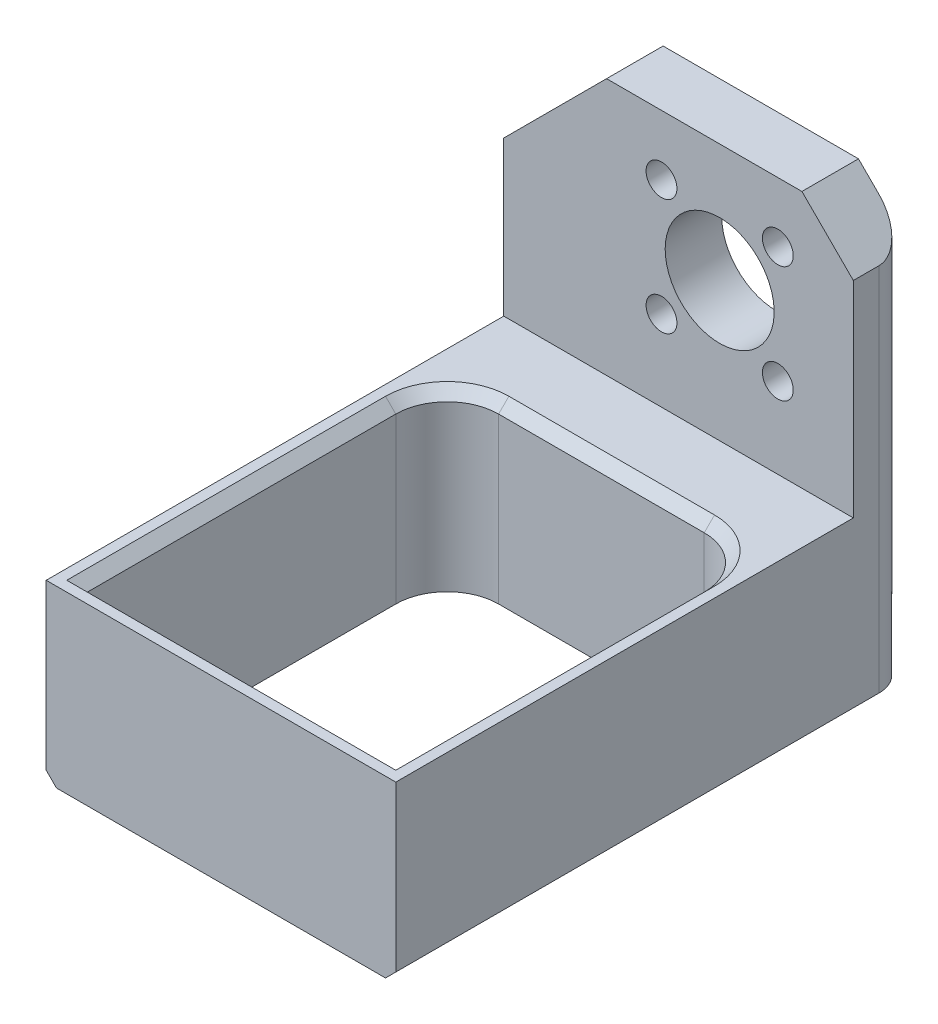
SolidWorks part; units mm, degrees
ref_plane "Płaszczyzna przednia" through (0, 0, 0) normal (0, 0, 1) x (1, 0, 0)
ref_plane "Płaszczyzna górna" through (0, 0, 0) normal (0, 1, 0) x (1, 0, 0)
ref_plane "Płaszczyzna prawa" through (0, 0, 0) normal (1, 0, 0) x (0, 0, -1)
sketch "Szkic1" plane through (0, 0, 0) normal (0, 1, 0) x (1, 0, 0)
  line L1 (-17, 25) -> (17, 25)
  line L2 (-17, 25) -> (-17, -25)
  line L3 (-17, -25) -> (17, -25)
  line L4 (17, 25) -> (17, -25)
  line L5 (-17, 25) -> (17, -25) construction
  line L6 (-17, -25) -> (17, 25) construction
  point P0 (0, 0)
  dimension "D1" = 34
  dimension "D2" = 50
extrude "Dodanie-wyciągnięcie1" add sketch "Szkic1" along normal blind 17
sketch "Szkic2" plane through (0, 17, 0) normal (0, 1, 0) x (1, 0, 0)
  line L0 (0, 25) -> (0, -25) construction
  line L1 (17, 25) -> (-17, 25) construction
  line L2 (-17, -25) -> (17, -25) construction
  line L3 (-17, 25) -> (-17, -25) construction
  line L4 (15, 7) -> (-15, 7)
  line L5 (15, 7) -> (15, -23)
  line L6 (15, -23) -> (-15, -23)
  line L7 (-15, 7) -> (-15, -23)
  line L8 (15, 7) -> (-15, -23) construction
  line L9 (15, -23) -> (-15, 7) construction
  point P6 (0, -8)
  dimension "D1" = 2
  dimension "D2" = 2
  dimension "D3" = 30
extrude "Wytnij-wyciągnięcie1" cut sketch "Szkic2" against normal blind 20
sketch "Szkic3" plane through (0, 17, 0) normal (0, 1, 0) x (1, 0, 0)
  line L0 (17, -25) -> (17, 25) construction
  line L1 (17, 25) -> (-17, 25)
  line L2 (17, 25) -> (17, 19.5)
  line L3 (17, 19.5) -> (-17, 19.5)
  line L4 (-17, 25) -> (-17, 19.5)
  line L5 (17, 25) -> (-17, 25) construction
  line L6 (-17, 25) -> (-17, -25) construction
  line L7 (-17, -25) -> (17, -25) construction
  dimension "D1" = 44.5
extrude "Dodanie-wyciągnięcie2" add sketch "Szkic3" along normal blind 25
sketch "Szkic4" plane through (0, 0, -25) normal (0, 0, -1) x (-1, 0, 0)
  line L1 (-4, 30.5) -> (-9.6569, 36.1569) construction
  line L2 (-4, 30.5) -> (-4, 38.5) construction
  line L3 (-17, 42) -> (17, 42) construction
  line L4 (0, 0) -> (0, 62.7345) construction
  line L6 (-17, 0) -> (17, 0) construction
  circle A0 centre (1.6569, 36.1569) radius 1.5
  circle A1 centre (-4, 30.5) radius 5.3
  circle A2 centre (-4, 30.5) radius 8
  circle A3 centre (-9.6569, 36.1569) radius 1.5
  circle A4 centre (-4, 30.5) radius 8
  circle A5 centre (1.6569, 24.8431) radius 1.5
  circle A6 centre (-4, 30.5) radius 8
  circle A7 centre (-9.6569, 24.8431) radius 1.5
  circle A8 centre (-4, 30.5) radius 8
  point P21 (-4, 30.5)
  dimension "D1" = 4
  dimension "D2" = 11.5
  dimension "D3" = 10.6
  dimension "D4" = 16
  dimension "D5" = 3
  dimension "D6" = 45
  dimension "D7" = 4
extrude "Wytnij-wyciągnięcie2" cut sketch "Szkic4" against normal blind 25 contours A2 A3 | A2 A3 | A2 A0 | A0 A2 | A6 A7 | A6 A7 | A4 A5 | A4 A5 | A1 region at (-2.0886, 36.5886, -25) region at (-1.1893, 35.6893, -25) region at (9.1893, 35.6893, -25) region at (10.0886, 36.5886, -25) region at (-2.0886, 24.4114, -25) region at (-1.1893, 25.3107, -25) region at (9.1893, 25.3107, -25) region at (10.0886, 24.4114, -25) region at (4, 30.5, -25)
chamfer "Sfazowanie1" distance 10 angle 45 1 edges at (-17, 42, -22.25)
chamfer "Sfazowanie2" distance 5 angle 45 1 edges at (17, 42, -22.25)
fillet "Zaokrąglenie1" radius 3 2 edges at (17, 18.5, -25) (-17, 16, -25)
sketch "Szkic5" plane through (0, 0, -7) normal (0, 0, 1) x (1, 0, 0)
  line L0 (15, 17) -> (-15, 17) construction
  line L1 (-15, 17) -> (15, 17)
  line L2 (-15, 17) -> (-15, 0)
  line L3 (-15, 0) -> (15, 0)
  line L4 (15, 17) -> (15, 0)
extrude "Wytnij-wyciągnięcie3" cut sketch "Szkic5" against normal blind 5
fillet "Zaokrąglenie2" radius 5 2 edges at (15, 8.5, -12) (-15, 8.5, -12)
chamfer "Sfazowanie3" distance 1 angle 45 6 edges at (13.5355, 17, -10.5355) (-13.5355, 17, -10.5355) (15, 17, 8) (0, 17, 23) (-15, 17, 8) (0, 17, -12)
chamfer "Sfazowanie4" distance 1 angle 45 5 edges at (17, 0, 1.5) (-17, 0, 1.5) (16.1213, 0, -24.1213) (-16.1213, 0, -24.1213) (0, 0, -25)
